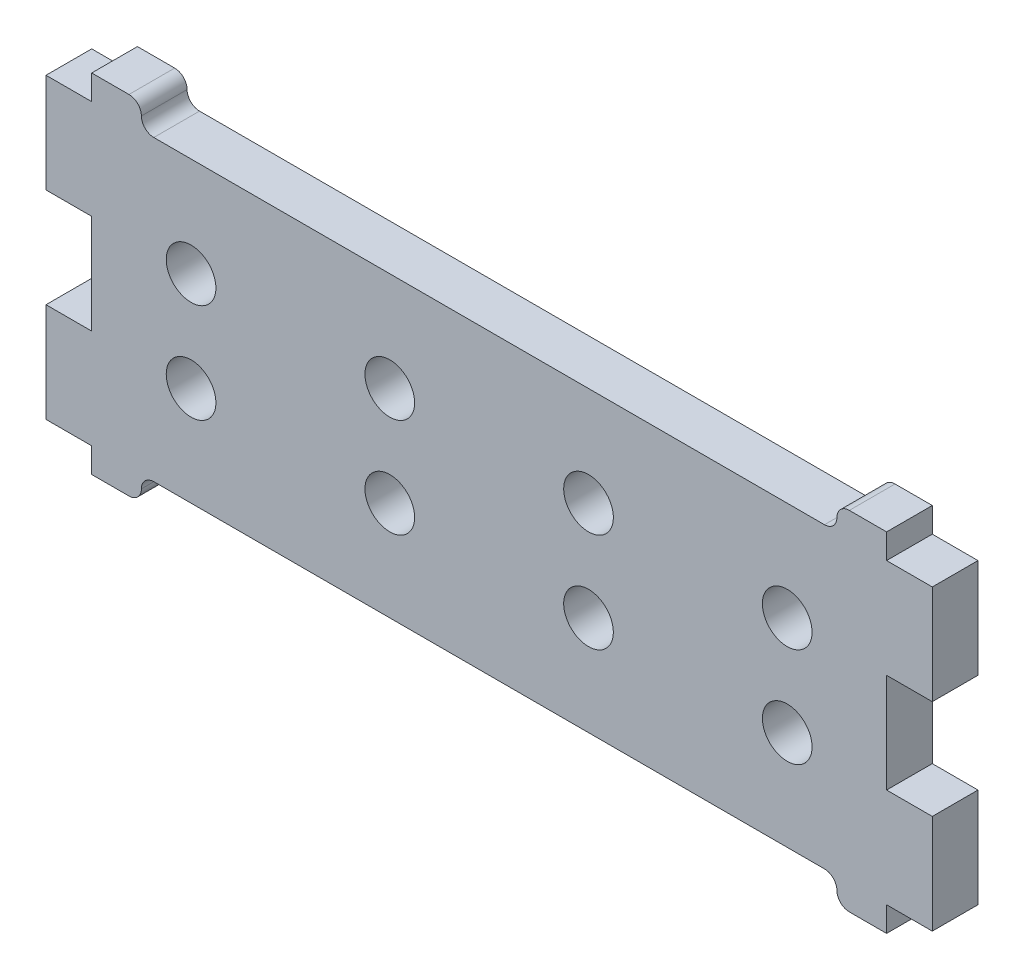
SolidWorks part; units mm, degrees
ref_plane "Front Plane" through (0, 0, 0) normal (0, 0, 1) x (1, 0, 0)
ref_plane "Top Plane" through (0, 0, 0) normal (0, 1, 0) x (1, 0, 0)
ref_plane "Right Plane" through (0, 0, 0) normal (1, 0, 0) x (0, 0, -1)
sketch "Sketch1" plane through (0, 0, 0) normal (0, 0, 1) x (1, 0, 0)
  line L0 (-56.642, -12.7) -> (-50.8, -12.7) construction
  line L1 (50.8, -22.225) -> (44.45, -22.225)
  line L2 (50.8, -22.225) -> (50.8, -19.05)
  line L3 (50.8, 22.225) -> (44.45, 22.225)
  line L4 (-50.8, -22.225) -> (-50.8, -19.05)
  line L5 (0, 22.225) -> (0, -22.225) construction
  line L6 (50.8, 0) -> (-50.8, 0) construction
  line L7 (-56.642, 6.35) -> (-50.8, 6.35)
  line L8 (-56.642, 6.35) -> (-56.642, 19.05)
  line L9 (-56.642, 19.05) -> (-50.8, 19.05)
  line L10 (-50.8, -6.35) -> (-50.8, 6.35)
  line L11 (-53.721, 19.05) -> (-53.721, 6.35) construction
  line L12 (-56.642, 12.7) -> (-50.8, 12.7) construction
  line L13 (-53.721, -19.05) -> (-53.721, -6.35) construction
  line L14 (50.8, -6.35) -> (50.8, 6.35)
  line L15 (-56.642, -19.05) -> (-50.8, -19.05)
  line L16 (-56.642, -6.35) -> (-56.642, -19.05)
  line L17 (-56.642, -6.35) -> (-50.8, -6.35)
  line L18 (53.721, -19.05) -> (53.721, -6.35) construction
  line L19 (56.642, 12.7) -> (50.8, 12.7) construction
  line L20 (53.721, 19.05) -> (53.721, 6.35) construction
  line L21 (56.642, -12.7) -> (50.8, -12.7) construction
  line L22 (56.642, -6.35) -> (50.8, -6.35)
  line L23 (56.642, -6.35) -> (56.642, -19.05)
  line L24 (56.642, -19.05) -> (50.8, -19.05)
  line L25 (50.8, 19.05) -> (50.8, 22.225)
  line L26 (50.8, 19.05) -> (50.8, 22.225)
  line L27 (56.642, 19.05) -> (50.8, 19.05)
  line L28 (56.642, 6.35) -> (56.642, 19.05)
  line L29 (56.642, 6.35) -> (50.8, 6.35)
  line L30 (50.8, -22.225) -> (50.8, -19.05)
  line L31 (-50.8, 19.05) -> (-50.8, 22.225)
  line L32 (-44.45, 19.05) -> (44.45, 19.05)
  line L33 (44.45, -19.05) -> (-44.45, -19.05)
  line L34 (-44.45, -19.05) -> (-44.45, -22.225)
  line L35 (-44.45, 22.225) -> (-44.45, 19.05)
  line L36 (44.45, 22.225) -> (44.45, 19.05)
  line L37 (-44.45, 22.225) -> (-50.8, 22.225)
  line L38 (-44.45, -22.225) -> (-50.8, -22.225)
  line L39 (44.45, -19.05) -> (44.45, -22.225)
  line L40 (50.8, -6.35) -> (50.8, 6.35)
  point P0 (0, 0)
  point P4 (-53.721, 12.7)
  point P22 (-53.721, -12.7)
  point P39 (53.721, -12.7)
  point P40 (53.721, 12.7)
  dimension "D1" = 101.6
  dimension "D2" = 44.45
  dimension "D3" = 12.7
  dimension "D4" = 5.842
  dimension "D5" = 3.175
  dimension "D6" = 6.35
extrude "Boss-Extrude1" add sketch "Sketch1" along normal blind 5.842 contours L33 L39 L1 L2 L30 L14 L29 L28 L27 L25 L3 L36 L32 L35 L37 L31 L9 L8 L7 L10 L17 L16 L15 L4 L38 L34 region at (0, 0, 0)
fillet "Fillet1" radius 1.5875 8 edges at (-44.45, -22.225, 2.921) (-44.45, -19.05, 2.921) (44.45, -22.225, 2.921) (44.45, -19.05, 2.921) (44.45, 19.05, 2.921) (44.45, 22.225, 2.921) (-44.45, 19.05, 2.921) (-44.45, 22.225, 2.921)
sketch "Sketch2" plane through (0, 0, 5.842) normal (0, 0, 1) x (1, 0, 0)
  line L0 (-50.8, 6.35) -> (50.8, 6.35) construction
  line L1 (50.8, 6.35) -> (50.8, -6.35) construction
  line L2 (50.8, -6.35) -> (-50.8, -6.35) construction
  line L3 (-50.8, -6.35) -> (-50.8, 6.35) construction
  line L4 (-56.642, -6.35) -> (-50.8, -6.35) construction
  line L5 (0, 19.05) -> (0, -19.05) construction
  line L6 (-42.8625, 19.05) -> (42.8625, 19.05) construction
  line L7 (42.8625, -19.05) -> (-42.8625, -19.05) construction
  line L8 (-50.8, 0) -> (50.8, 0) construction
  circle A0 centre (-38.1, 6.35) radius 3.175
  circle A2 centre (-12.7, 6.35) radius 3.175
  circle A3 centre (-12.7, -6.35) radius 3.175
  circle A5 centre (-38.1, -6.35) radius 3.175
  circle A6 centre (38.1, -6.35) radius 3.175
  circle A8 centre (12.7, -6.35) radius 3.175
  circle A9 centre (12.7, 6.35) radius 3.175
  circle A11 centre (38.1, 6.35) radius 3.175
  circle A12 centre (-25.4, 6.35) radius 3.175 [skipped]
  dimension "D1" = 12.7
  dimension "D2" = 3
extrude "Cut-Extrude1" cut sketch "Sketch2" against normal through all
